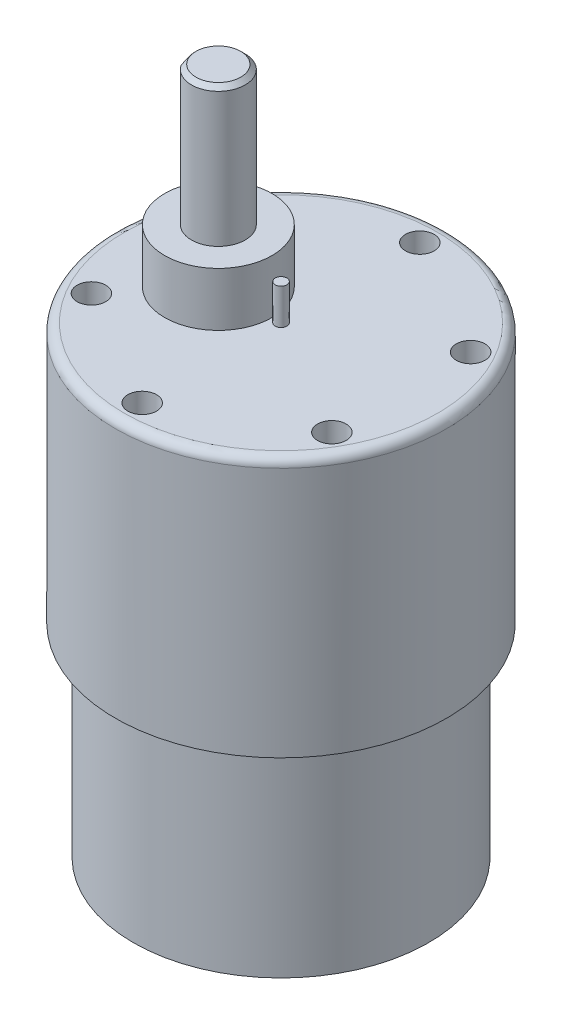
SolidWorks part; units mm, degrees
material "AISI 1020"
ref_plane "Спереди" through (0, 0, 0) normal (0, 0, 1) x (1, 0, 0)
ref_plane "Сверху" through (0, 0, 0) normal (0, 1, 0) x (1, 0, 0)
ref_plane "Справа" through (0, 0, 0) normal (1, 0, 0) x (0, 0, -1)
sketch "Эскиз1" plane through (0, 0, 0) normal (0, 1, 0) x (1, 0, 0)
  circle A0 centre (0, 0) radius 7.5
  dimension "D1" = 15
extrude "Бобышка-Вытянуть1" add sketch "Эскиз1" along normal blind 5
sketch "Эскиз2" plane through (0, 5, 0) normal (0, 1, 0) x (1, 0, 0)
  circle A0 centre (0, 0) radius 16.5
  dimension "D1" = 33
extrude "Бобышка-Вытянуть2" add sketch "Эскиз2" along normal blind 22.7
sketch "Эскиз3" plane through (0, 27.7, 0) normal (0, 1, 0) x (1, 0, 0)
  circle A0 centre (0, 0) radius 18.5
  dimension "D1" = 37
extrude "Бобышка-Вытянуть3" add sketch "Эскиз3" along normal blind 29
sketch "Эскиз4" plane through (0, 56.7, 0) normal (0, 1, 0) x (1, 0, 0)
  circle A1 centre (0, -15.5) radius 1.6
  circle A2 centre (-13.4234, -7.75) radius 1.6
  circle A3 centre (-13.4234, 7.75) radius 1.6
  circle A4 centre (0, 15.5) radius 1.6
  circle A5 centre (13.4234, 7.75) radius 1.6
  circle A6 centre (13.4234, -7.75) radius 1.6
  point P17 (0, 0)
  dimension "D2" = 3.2
  dimension "D3" = 6
extrude "Вырез-Вытянуть1" cut sketch "Эскиз4" against normal blind 10
sketch "Эскиз5" plane through (0, 56.7, 0) normal (0, 1, 0) x (1, 0, 0)
  circle A0 centre (-7, 0) radius 6
  dimension "D2" = 12
  dimension "D1" = 7
extrude "Бобышка-Вытянуть4" add sketch "Эскиз5" along normal blind 6
sketch "Эскиз6" plane through (0, 62.7, 0) normal (0, 1, 0) x (1, 0, 0)
  circle A0 centre (-7, 0) radius 3
  dimension "D2" = 6
extrude "Бобышка-Вытянуть5" add sketch "Эскиз6" along normal blind 15.5
sketch "Эскиз7" plane through (0, 78.2, 0) normal (0, 1, 0) x (1, 0, 0)
  line L0 (-9.5333, 1.6069) -> (-9.4656, -1.709)
  circle A1 centre (-7, 0) radius 3
  arc A2 (-9.5333, 1.6069) -> (-9.4656, -1.709) centre (-7, 0) ccw
  dimension "D2" = 2.5
  dimension "D1" = 0
extrude "Вырез-Вытянуть2" cut sketch "Эскиз7" against normal blind 12
chamfer "Фаска1" distance 0.5 angle 45 1 edges at (-4.0006, 78.2, -0.0612)
fillet "Скругление1" radius 1 1 edges at (0, 56.7, 18.5)
fillet "Скругление2" radius 1 1 edges at (0, 27.7, 16.5)
fillet "Скругление3" radius 1 1 edges at (0, 0, 7.5)
sketch "Эскиз8" plane through (0, 56.7, 0) normal (0, 1, 0) x (1, 0, 0)
  circle A0 centre (0, 0) radius 0.6543
extrude "Бобышка-Вытянуть6" add sketch "Эскиз8" along normal blind 4
